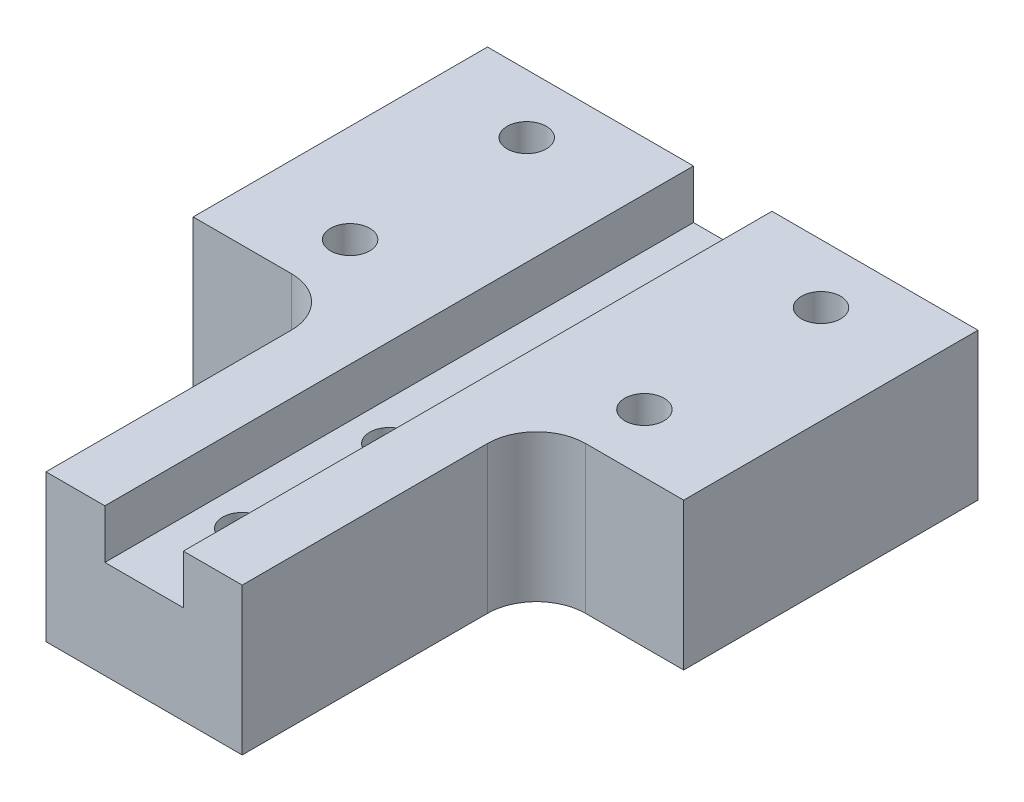
SolidWorks part; units mm, degrees
ref_plane "Front Plane" through (0, 0, 0) normal (0, 0, 1) x (1, 0, 0)
ref_plane "Top Plane" through (0, 0, 0) normal (0, 1, 0) x (1, 0, 0)
ref_plane "Right Plane" through (0, 0, 0) normal (1, 0, 0) x (0, 0, -1)
sketch "Sketch1" plane through (0, 0, 0) normal (0, 1, 0) x (1, 0, 0)
  line L0 (0, -55) -> (0, 55) construction
  line L1 (-25, 15) -> (25, 15)
  line L2 (-25, 15) -> (-25, -15)
  line L3 (-25, -15) -> (25, -15)
  line L4 (25, 15) -> (25, -15)
  line L5 (-25, 15) -> (25, -15) construction
  line L6 (-25, -15) -> (25, 15) construction
  line L7 (-15, 9) -> (15, 9)
  line L8 (-15, 9) -> (-15, -9) construction
  line L9 (-15, -9) -> (15, -9) construction
  line L10 (15, 9) -> (15, -9) construction
  line L11 (-15, 9) -> (15, -9) construction
  line L12 (-15, -9) -> (15, 9) construction
  line L13 (-10, -15) -> (10, -15)
  line L14 (-10, -15) -> (-10, -45)
  line L15 (-10, -45) -> (10, -45)
  line L16 (10, -15) -> (10, -45)
  circle A0 centre (-15, 9) radius 2
  circle A1 centre (15, 9) radius 2
  circle A2 centre (15, -9) radius 2
  circle A3 centre (-15, -9) radius 2
  circle A4 centre (0, -20) radius 2
  circle A5 centre (0, -35) radius 2
  point P0 (0, 0)
  point P6 (0, 0)
  dimension "D1" = 4
  dimension "D9" = 4
  dimension "D10" = 10
  dimension "D11" = 15
  dimension "D2" = 50
  dimension "D3" = 30
  dimension "D4" = 10
  dimension "D5" = 6
  dimension "D6" = 30
  dimension "D7" = 20
  dimension "D8" = 15
extrude "Boss-Extrude2" add sketch "Sketch1" against normal blind 15 contours L4 L1 L2 L3 A3 A2 A1 A0 region at (0, 0, 0)
extrude "Boss-Extrude3" add sketch "Sketch1<3>" against normal up to surface (15 mm away) contours L16 L3 L14 L15 A5 A4 region at (0, 0, 30.1093) up to face at (15, -15, -7)
sketch "Sketch1<3>" plane through (0, 0, 0) normal (0, 1, 0) x (1, 0, 0) same geometry as "Sketch1"
fillet "Fillet1" radius 5 2 edges at (10, -7.5, 15) (-10, -7.5, 15)
sketch "Sketch5" plane through (0, 0, 0) normal (0, 1, 0) x (1, 0, 0)
  line L0 (0, -55) -> (0, 55) construction
  line L1 (-4, 21.8624) -> (4, 21.8624)
  line L2 (-4, 21.8624) -> (-4, -48.1376)
  line L3 (-4, -48.1376) -> (4, -48.1376)
  line L4 (4, 21.8624) -> (4, -48.1376)
  line L5 (-4, 21.8624) -> (4, -48.1376) construction
  line L6 (-4, -48.1376) -> (4, 21.8624) construction
  point P0 (0, -13.1376)
  dimension "D1" = 8
  dimension "D2" = 70
extrude "Cut-Extrude1" cut sketch "Sketch5" against normal blind 5
